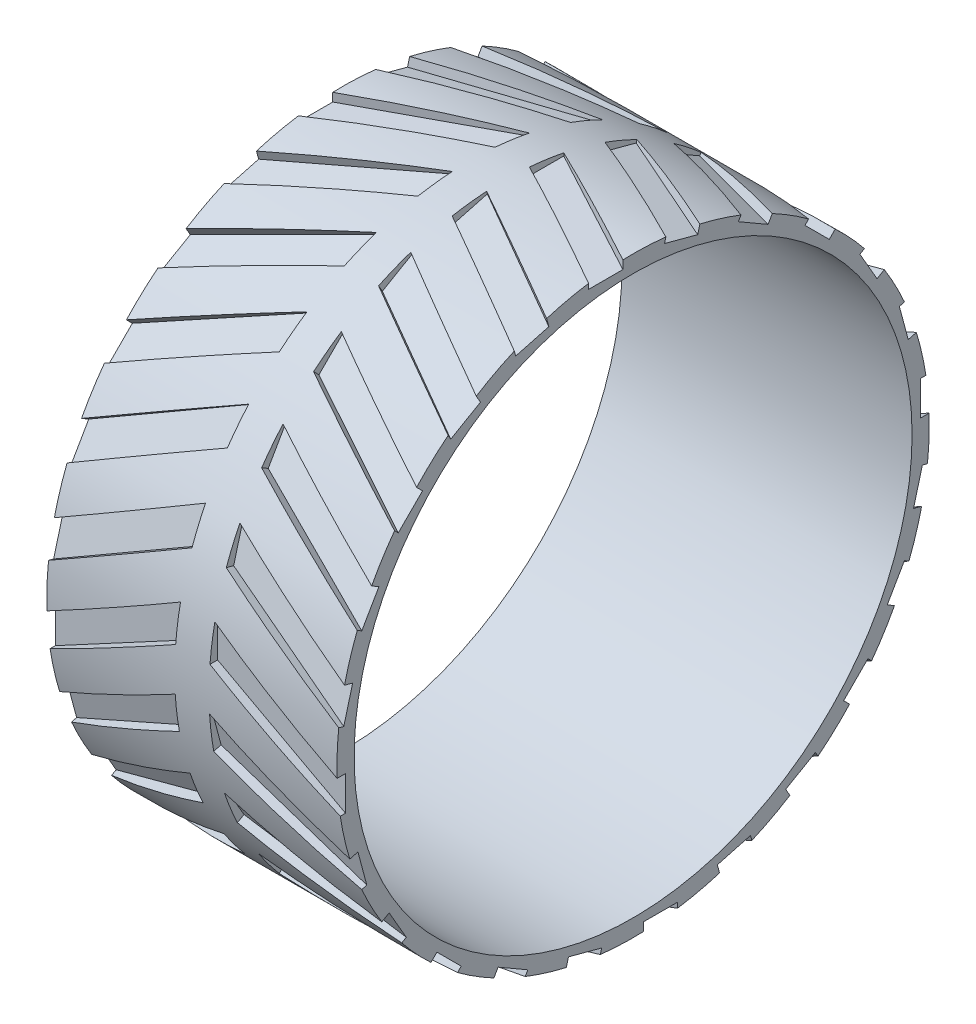
SolidWorks part; units mm, degrees
material "Silicon Rubber"
ref_plane "Front Plane" through (0, 0, 0) normal (0, 0, 1) x (1, 0, 0)
ref_plane "Top Plane" through (0, 0, 0) normal (0, 1, 0) x (1, 0, 0)
ref_plane "Right Plane" through (0, 0, 0) normal (1, 0, 0) x (0, 0, -1)
sketch "Sketch1" plane through (0, 0, 0) normal (1, 0, 0) x (0, 0, -1)
  circle A0 centre (0, 0) radius 32.5
  circle A1 centre (0, 0) radius 34.5
  dimension "D1" = 65
  dimension "D2" = 69
extrude "Boss-Extrude1" add sketch "Sketch1" along normal blind 33.8
ref_plane "Plane1" through (0, 33.5, 0) normal (0, 1, 0) x (1, 0, 0)
sketch "Sketch2" plane through (0, 33.5, 0) normal (0, 1, 0) x (1, 0, 0)
  line L0 (0, 0) -> (33.8, 0) construction
  line L1 (33.8, -34.5) -> (33.8, 34.5) construction
  line L2 (16.9, 49.2036) -> (16.9, -49.2036) construction
  line L3 (0, -1.1846) -> (16.9, 7.9004)
  line L4 (0, 34.5) -> (0, -34.5) construction
  line L5 (0, -1.1846) -> (0, -5.1846)
  line L6 (0, -5.1846) -> (16.9, 3.9004)
  line L7 (16.9, 7.9004) -> (16.9, 3.9004)
  line L8 (33.8, -1.1846) -> (33.8, -5.1846)
  line L9 (33.8, -5.1846) -> (16.9, 3.9004)
  line L10 (33.8, -1.1846) -> (16.9, 7.9004)
  point P8 (16.9, 0)
  dimension "D1" = 4
  dimension "D2" = 4
extrude "Cut-Extrude1" cut sketch "Sketch2" along normal blind 30.8 contours L7 L3 L5 L6 | L8 L10 L7 L9 region at (8.45, 33.5, -1.3579) region at (25.35, 33.5, -1.3579)
pattern_circular "CirPattern2" count 24 every 15 about axis through (33.8, 0, 0) along (-1, 0, 0) of "Cut-Extrude1" reverse direction yes
ref_plane "Plane2" through (16.9, 0, 0) normal (-1, 0, 0) x (0, 0, 1)
sketch "Sketch4" plane through (16.9, 0, 0) normal (-1, 0, 0) x (0, 0, 1)
  circle A0 centre (0, 0) radius 32.5
  circle A1 centre (0, 0) radius 34.5
extrude "Boss-Extrude2" add sketch "Sketch4" along normal blind 2 and the other way blind 2
